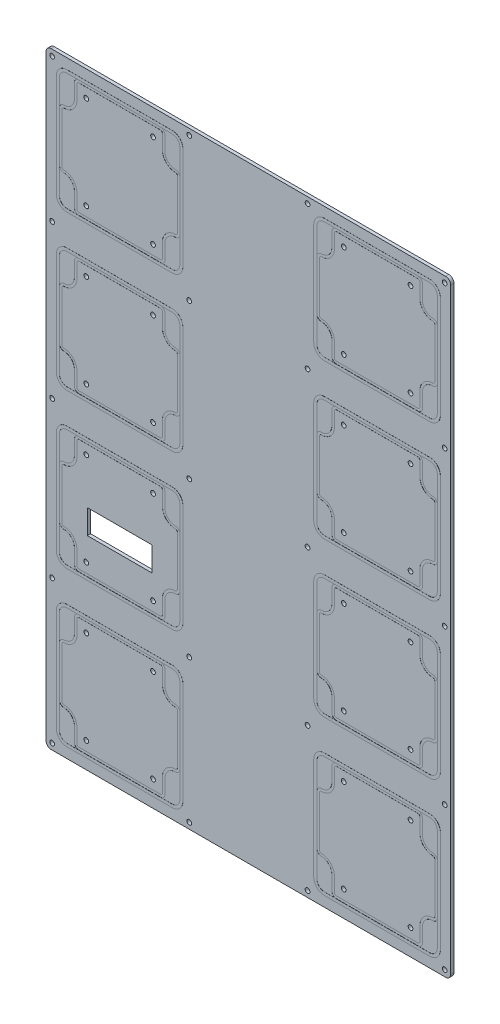
SolidWorks part; units mm, degrees
ref_plane "Front Plane" through (0, 0, 0) normal (0, 0, 1) x (1, 0, 0)
ref_plane "Top Plane" through (0, 0, 0) normal (0, 1, 0) x (1, 0, 0)
ref_plane "Right Plane" through (0, 0, 0) normal (1, 0, 0) x (0, 0, -1)
sketch "Sketch1" plane through (0, 0, 0) normal (0, 0, 1) x (1, 0, 0)
  line L1 (0, 0) -> (254, 0)
  line L2 (0, 0) -> (0, 381)
  line L3 (0, 381) -> (254, 381)
  line L4 (254, 0) -> (254, 381)
  dimension "D1" = 381
  dimension "D2" = 254
extrude "Boss-Extrude1" add sketch "Sketch1" along normal blind 2.032
sketch "Sketch2" plane through (0, 0, 2.032) normal (0, 0, 1) x (1, 0, 0)
  line L0 (89.8652, 377.19) -> (89.8652, 3.81) construction
  line L1 (0, 381) -> (254, 381) construction
  line L2 (127, 381) -> (127, 377.19) construction
  line L3 (3.81, 377.19) -> (250.19, 377.19) construction
  line L5 (164.1348, 377.19) -> (164.1348, 3.81) construction
  line L6 (3.81, 377.19) -> (3.81, 3.81) construction
  line L7 (3.81, 3.81) -> (250.19, 3.81) construction
  line L8 (250.19, 3.81) -> (250.19, 377.19) construction
  line L9 (3.81, 190.5) -> (250.19, 190.5) construction
  line L10 (3.81, 287.3756) -> (250.19, 287.3756) construction
  line L11 (3.81, 93.6244) -> (250.19, 93.6244) construction
  line L12 (0, 381) -> (0, 0) construction
  line L13 (0, 190.5) -> (3.81, 190.5) construction
  circle A0 centre (3.81, 377.19) radius 1.4732
  circle A1 centre (89.8652, 377.19) radius 1.4732
  circle A2 centre (164.1348, 377.19) radius 1.4732
  circle A3 centre (250.19, 377.19) radius 1.4732
  circle A4 centre (164.1348, 287.3755) radius 1.4732
  circle A5 centre (3.81, 287.3756) radius 1.4732
  circle A6 centre (250.19, 287.3756) radius 1.4732
  circle A7 centre (89.8652, 287.3756) radius 1.4732
  circle A8 centre (164.1348, 190.5) radius 1.4732
  circle A9 centre (3.81, 191.135) radius 1.4732
  circle A10 centre (250.19, 190.5) radius 1.4732
  circle A11 centre (89.8652, 190.5) radius 1.4732
  circle A12 centre (164.1348, 93.6244) radius 1.4732
  circle A13 centre (3.81, 93.6244) radius 1.4732
  circle A14 centre (250.19, 93.6244) radius 1.4732
  circle A15 centre (89.8652, 93.6244) radius 1.4732
  circle A16 centre (164.1348, 3.81) radius 1.4732
  circle A17 centre (3.81, 3.81) radius 1.4732
  circle A18 centre (250.19, 3.81) radius 1.4732
  circle A19 centre (89.8652, 3.81) radius 1.4732
  dimension "D6" = 2.9464
  dimension "D23" = 0
  dimension "D24" = 0
  dimension "D25" = 0
  dimension "D28" = 0
  dimension "D29" = 0
  dimension "D30" = 0
  dimension "D31" = 0
  dimension "D32" = 86.0552
  dimension "D1" = 246.38
  dimension "D3" = 373.38
  dimension "D4" = 96.8756
  dimension "D5" = 96.8756
  dimension "D7" = 86.0552
  dimension "D8" = 86.0552
  dimension "D9" = 0
  dimension "D10" = 0
  dimension "D11" = 0
  dimension "D12" = 86.0552
  dimension "D13" = 0
  dimension "D14" = 0
  dimension "D15" = 0
  dimension "D16" = 0
  dimension "D17" = 0
  dimension "D18" = 0
  dimension "D19" = 0
  dimension "D20" = 0
  dimension "D21" = 0
  dimension "D22" = 0
  dimension "D26" = 0
  dimension "D27" = 0
extrude "Cut-Extrude1" cut sketch "Sketch2" against normal through all
fillet "Fillet1" radius 3.175 4 edges at (254, 0, 1.016) (0, 0, 1.016) (254, 381, 1.016) (0, 381, 1.016)
sketch "Sketch3" plane through (0, 0, 2.032) normal (0, 0, 1) x (1, 0, 0)
  line L0 (9.9695, 45.1866) -> (46.2026, 45.1866) construction
  line L1 (46.2026, 45.1866) -> (46.2026, 9.9695) construction
  line L2 (81.2038, 28.3591) -> (82.4357, 28.3591) construction
  line L3 (82.4357, 29.591) -> (82.4357, 60.7822)
  line L4 (73.0377, 11.2014) -> (73.0377, 20.193)
  line L5 (81.2038, 62.0141) -> (82.4357, 62.0141) construction
  line L6 (71.8058, 9.9695) -> (20.5994, 9.9695)
  line L7 (19.3675, 11.2014) -> (19.3675, 20.193)
  line L8 (11.2014, 28.3591) -> (9.9695, 28.3591) construction
  line L9 (9.9695, 29.591) -> (9.9695, 60.7822)
  line L10 (73.0377, 79.1718) -> (73.0377, 70.1802)
  line L11 (71.8058, 80.4037) -> (20.5994, 80.4037)
  line L12 (3.175, 0) -> (250.825, 0) construction
  line L13 (0, 377.825) -> (0, 3.175) construction
  line L14 (11.2014, 62.0141) -> (9.9695, 62.0141) construction
  line L15 (19.3675, 79.1718) -> (19.3675, 70.1802)
  line L16 (17.78, 79.1718) -> (17.78, 70.1802)
  line L17 (8.382, 29.591) -> (8.382, 60.7822)
  line L18 (17.78, 11.2014) -> (17.78, 20.193)
  line L19 (71.8058, 8.382) -> (20.5994, 8.382)
  line L20 (74.6252, 11.2014) -> (74.6252, 20.193)
  line L21 (84.0232, 29.591) -> (84.0232, 60.7822)
  line L22 (74.6252, 79.1718) -> (74.6252, 70.1802)
  line L23 (71.8058, 81.9912) -> (20.5994, 81.9912)
  arc A0 (19.3675, 20.193) -> (11.2014, 28.3591) centre (11.2014, 20.193) ccw
  arc A1 (9.9695, 29.591) -> (11.2014, 28.3591) centre (11.2014, 29.591) ccw
  arc A2 (19.3675, 11.2014) -> (20.5994, 9.9695) centre (20.5994, 11.2014) ccw
  arc A3 (73.0377, 11.2014) -> (71.8058, 9.9695) centre (71.8058, 11.2014) cw
  arc A4 (82.4357, 29.591) -> (81.2038, 28.3591) centre (81.2038, 29.591) cw
  arc A5 (73.0377, 20.193) -> (81.2038, 28.3591) centre (81.2038, 20.193) cw
  arc A6 (73.0377, 70.1802) -> (81.2038, 62.0141) centre (81.2038, 70.1802) ccw
  arc A7 (82.4357, 60.7822) -> (81.2038, 62.0141) centre (81.2038, 60.7822) ccw
  arc A8 (73.0377, 79.1718) -> (71.8058, 80.4037) centre (71.8058, 79.1718) ccw
  arc A9 (19.3675, 79.1718) -> (20.5994, 80.4037) centre (20.5994, 79.1718) cw
  arc A10 (9.9695, 60.7822) -> (11.2014, 62.0141) centre (11.2014, 60.7822) cw
  arc A11 (19.3675, 70.1802) -> (11.2014, 62.0141) centre (11.2014, 70.1802) cw
  arc A12 (17.78, 70.1802) -> (11.2014, 63.6016) centre (11.2014, 70.1802) cw
  arc A13 (8.382, 60.7822) -> (11.2014, 63.6016) centre (11.2014, 60.7822) cw
  arc A14 (8.382, 29.591) -> (11.2014, 26.7716) centre (11.2014, 29.591) ccw
  arc A15 (17.78, 20.193) -> (11.2014, 26.7716) centre (11.2014, 20.193) ccw
  arc A16 (17.78, 11.2014) -> (20.5994, 8.382) centre (20.5994, 11.2014) ccw
  arc A17 (74.6252, 11.2014) -> (71.8058, 8.382) centre (71.8058, 11.2014) cw
  arc A18 (74.6252, 20.193) -> (81.2038, 26.7716) centre (81.2038, 20.193) cw
  arc A19 (84.0232, 29.591) -> (81.2038, 26.7716) centre (81.2038, 29.591) cw
  arc A20 (84.0232, 60.7822) -> (81.2038, 63.6016) centre (81.2038, 60.7822) ccw
  arc A21 (74.6252, 70.1802) -> (81.2038, 63.6016) centre (81.2038, 70.1802) ccw
  arc A22 (74.6252, 79.1718) -> (71.8058, 81.9912) centre (71.8058, 79.1718) ccw
  arc A23 (17.78, 79.1718) -> (20.5994, 81.9912) centre (20.5994, 79.1718) cw
  point P35 (82.4357, 45.1866)
  dimension "D6" = 8.1661
  dimension "D7" = 2.4638
  dimension "D8" = 1.2319
  dimension "D1" = 9.9695
  dimension "D2" = 9.9695
  dimension "D3" = 19.3675
  dimension "D4" = 28.3591
  dimension "D5" = 45.1866
  dimension "D10" = 46.2026
  dimension "D9" = 1.5875
extrude "Cut-Extrude2" cut sketch "Sketch3" against normal blind 0.0508
sketch "Sketch4" plane through (0, 0, 2.032) normal (0, 0, 1) x (1, 0, 0)
  line L0 (8.382, 60.7822) -> (8.382, 77.2287)
  line L1 (13.1445, 81.9912) -> (20.5994, 81.9912)
  line L2 (20.5994, 81.9912) -> (79.2607, 81.9912)
  line L3 (84.0232, 77.2287) -> (84.0232, 13.1445)
  line L4 (79.2607, 8.382) -> (13.1445, 8.382)
  line L5 (8.382, 13.1445) -> (8.382, 60.7822)
  line L6 (6.477, 60.7822) -> (6.477, 77.2287)
  line L7 (13.1445, 83.8962) -> (20.5994, 83.8962)
  line L8 (20.5994, 83.8962) -> (79.2607, 83.8962)
  line L9 (85.9282, 77.2287) -> (85.9282, 13.1445)
  line L10 (79.2607, 6.477) -> (13.1445, 6.477)
  line L11 (6.477, 13.1445) -> (6.477, 60.7822)
  arc A0 (13.1445, 81.9912) -> (8.382, 77.2287) centre (13.1445, 77.2287) ccw
  arc A1 (79.2607, 81.9912) -> (84.0232, 77.2287) centre (79.2607, 77.2287) cw
  arc A2 (84.0232, 13.1445) -> (79.2607, 8.382) centre (79.2607, 13.1445) cw
  arc A3 (8.382, 13.1445) -> (13.1445, 8.382) centre (13.1445, 13.1445) ccw
  arc A4 (13.1445, 83.8962) -> (6.477, 77.2287) centre (13.1445, 77.2287) ccw
  arc A5 (79.2607, 83.8962) -> (85.9282, 77.2287) centre (79.2607, 77.2287) cw
  arc A6 (85.9282, 13.1445) -> (79.2607, 6.477) centre (79.2607, 13.1445) cw
  arc A7 (6.477, 13.1445) -> (13.1445, 6.477) centre (13.1445, 13.1445) ccw
  dimension "D1" = 4.7625
  dimension "D2" = 1.905
extrude "Boss-Extrude2" add sketch "Sketch4" along normal blind 0.0508
sketch "Sketch5" plane through (0, 0, 2.032) normal (0, 0, 1) x (1, 0, 0)
  line L0 (9.9695, 45.1866) -> (82.4357, 45.1866) construction
  line L1 (9.9695, 60.7822) -> (9.9695, 29.591) construction
  line L2 (82.4357, 29.591) -> (82.4357, 60.7822) construction
  line L3 (82.4357, 45.1866) -> (46.2026, 45.1866) construction
  line L4 (46.2026, 45.1866) -> (46.2026, 80.4037) construction
  line L5 (71.8058, 80.4037) -> (20.5994, 80.4037) construction
  circle A0 centre (25.2476, 74.3966) radius 1.4732
  circle A1 centre (67.1576, 74.3966) radius 1.4732
  circle A2 centre (67.1576, 15.9766) radius 1.4732
  circle A3 centre (25.2476, 15.9766) radius 1.4732
  dimension "D1" = 2.9464
  dimension "D2" = 20.955
  dimension "D3" = 29.21
extrude "Cut-Extrude3" cut sketch "Sketch5" against normal through all
pattern_linear "LPattern1" count 4 spacing 96.8756 along (0, 1, 0) count 2 spacing 161.5948 along (1, 0, 0) of "Cut-Extrude2", "Boss-Extrude2", "Cut-Extrude3"
sketch "Sketch6" plane through (0, 0, 2.032) normal (0, 0, 1) x (1, 0, 0)
  line L0 (25.8826, 135.255) -> (9.9695, 135.255) construction
  line L1 (25.8826, 142.875) -> (66.5226, 142.875)
  line L2 (25.8826, 142.875) -> (25.8826, 127.635)
  line L3 (25.8826, 127.635) -> (66.5226, 127.635)
  line L4 (66.5226, 142.875) -> (66.5226, 127.635)
  line L5 (9.9695, 157.6578) -> (9.9695, 126.4666) construction
  line L6 (66.5226, 135.255) -> (82.4357, 135.255) construction
  line L7 (82.4357, 126.4666) -> (82.4357, 157.6578) construction
  line L8 (250.825, 381) -> (3.175, 381) construction
  line L10 (46.2026, 127.635) -> (46.2026, 106.8451) construction
  line L11 (20.5994, 106.8451) -> (71.8058, 106.8451) construction
  dimension "D1" = 15.24
  dimension "D2" = 40.64
  dimension "D3" = 238.125
extrude "Cut-Extrude4" cut sketch "Sketch6" against normal through all
